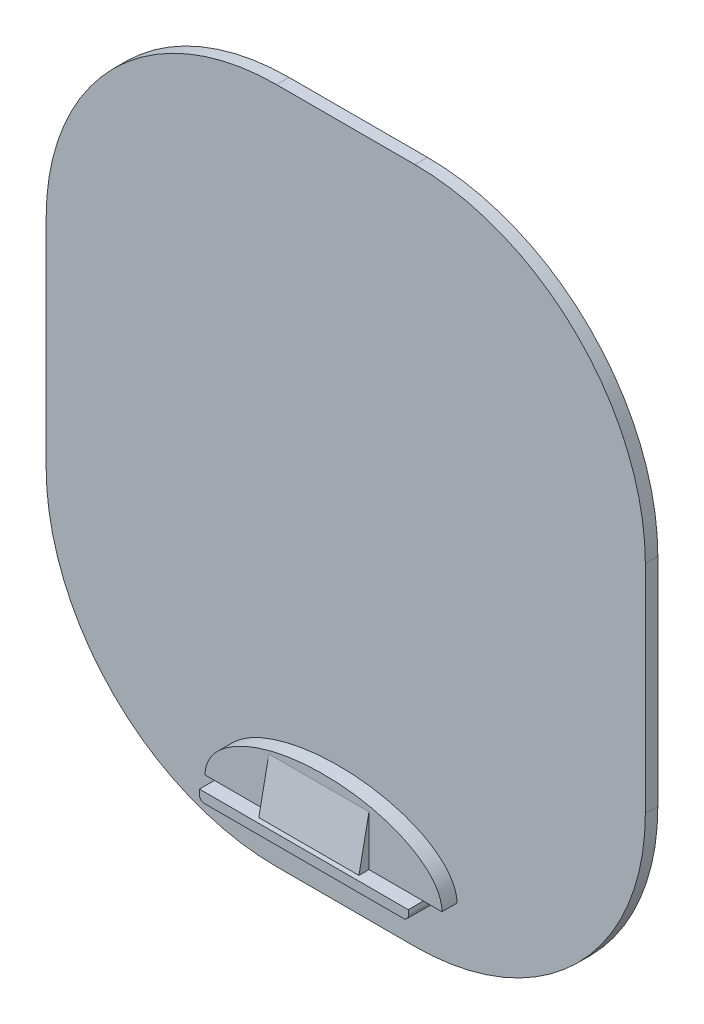
SolidWorks part; units mm, degrees
note: The reader was unsure of these and kept them because the rebuilt part matched: shared geometry of "Sketch15<3>".
ref_plane "Front Plane" through (0, 0, 0) normal (0, 0, 1) x (1, 0, 0)
ref_plane "Top Plane" through (0, 0, 0) normal (0, 1, 0) x (1, 0, 0)
ref_plane "Right Plane" through (0, 0, 0) normal (1, 0, 0) x (0, 0, -1)
sketch "Sketch1" plane through (0, 0, 0) normal (0, 0, 1) x (1, 0, 0)
  line L53 (241.5433, 205.3413) -> (246.9652, 204.9327)
  line L72 (-6.9957, 198.2293) -> (-6.9957, -78.6307)
  line L73 (35.8033, 153.9063) -> (35.8033, -34.3077)
  line L74 (69.2043, 274.4293) -> (259.7043, 274.4293)
  line L75 (335.9043, 198.2293) -> (335.9043, -78.6307)
  line L76 (259.7043, -154.8307) -> (69.2043, -154.8307)
  line L77 (87.2383, 205.3413) -> (241.5433, 205.3413)
  line L78 (35.8033, 153.9063) -> (35.8033, -34.3077)
  line L79 (87.2383, -85.7427) -> (238.612, -85.7427)
  line L80 (292.9783, 152.6781) -> (292.9783, -34.3077)
  line L81 (87.2383, -85.7427) -> (238.612, -85.7427)
  line L82 (292.9783, -34.3077) -> (292.9783, 152.6781)
  line L83 (241.5433, 205.3413) -> (87.2383, 205.3413)
  line L84 (-6.9957, 198.2293) -> (-6.9957, -78.6307)
  line L85 (69.2043, -154.8307) -> (259.7043, -154.8307)
  line L86 (335.9043, -78.6307) -> (335.9043, 198.2293)
  line L87 (259.7043, 274.4293) -> (69.2043, 274.4293)
  arc A32 (35.8033, -34.3077) -> (87.2383, -85.7427) centre (87.2383, -34.3077) ccw
  arc A33 (238.612, -85.7427) -> (292.9783, -34.3077) centre (238.612, -31.2928) ccw
  arc A34 (292.9783, 152.6781) -> (241.5433, 205.3413) centre (240.3004, 152.6781) ccw
  arc A35 (87.2383, 205.3413) -> (35.8033, 153.9063) centre (87.2383, 153.9063) ccw
  arc A36 (-6.9957, -78.6307) -> (69.2043, -154.8307) centre (69.2043, -78.6307) ccw
  arc A37 (259.7043, -154.8307) -> (335.9043, -78.6307) centre (259.7043, -78.6307) ccw
  arc A38 (335.9043, 198.2293) -> (259.7043, 274.4293) centre (259.7043, 198.2293) ccw
  arc A39 (69.2043, 274.4293) -> (-6.9957, 198.2293) centre (69.2043, 198.2293) ccw
  point P7 (-1548.8445, 807.057)
  point P171 (69.2043, 274.4293)
  point P172 (259.7043, 274.4293)
  point P173 (335.9043, 198.2293)
  point P174 (335.9043, -78.6307)
  point P175 (87.2383, 205.3413)
  point P176 (241.5433, 205.3413)
  point P181 (292.9783, 152.6781)
  point P182 (292.9783, -34.3077)
  point P183 (241.5433, -85.7427)
  point P184 (87.2383, -85.7427)
  point P185 (35.8033, -34.3077)
  point P186 (35.8033, 153.9063)
  point P187 (259.7043, -154.8307)
  point P188 (69.2043, -154.8307)
  point P200 (-6.9957, -78.6307)
  point P202 (-6.9957, 198.2293)
ref_plane "Plane1" through (0, 0, 10.16) normal (0, 0, 1) x (1, 0, 0)
ref_plane "Plane2" through (0, 0, 8.89) normal (0, 0, 1) x (1, 0, 0)
sketch "Sketch14" plane through (0, 0, 8.89) normal (0, 0, 1) x (1, 0, 0)
  line L20 (198.2363, 213.4693) -> (127.9259, 213.4693)
  line L21 (11.0859, -13.2857) -> (11.0859, 96.6293)
  line L22 (198.2363, -130.1257) -> (127.9259, -130.1257)
  line L23 (315.0763, 96.6293) -> (315.0763, -13.2857)
  arc A8 (315.0763, 96.6293) -> (198.2363, 213.4693) centre (198.2363, 96.6293) ccw
  arc A9 (127.9259, 213.4693) -> (11.0859, 96.6293) centre (127.9259, 96.6293) ccw
  arc A10 (127.9259, -130.1257) -> (11.0859, -13.2857) centre (127.9259, -13.2857) cw
  arc A11 (315.0763, -13.2857) -> (198.2363, -130.1257) centre (198.2363, -13.2857) cw
extrude "Boss-Extrude3" add sketch "Sketch14" along normal blind 6.35
sketch "Sketch15" plane through (0, 0, 15.24) normal (0, 0, 1) x (1, 0, 0)
  line L0 (99.3113, -100.3592) -> (219.5215, -100.3592)
  line L2 (99.3113, -100.3592) -> (219.5215, -100.3592)
  line L4 (106.6408, -105.4392) -> (207.5293, -105.4392)
  line L6 (104.1008, -100.3592) -> (210.0693, -100.3592)
  line L7 (104.1008, -100.3592) -> (104.1008, -102.8992)
  line L8 (104.1008, -105.4392) -> (210.0693, -105.4392)
  line L9 (210.0693, -100.3592) -> (210.0693, -102.8992)
  arc A0 (207.5293, -105.4392) -> (210.0693, -102.8992) centre (207.5293, -102.8992) ccw
  arc A1 (106.6408, -105.4392) -> (104.1008, -102.8992) centre (106.6408, -102.8992) cw
  ellipse E0 centre (159.4164, -100.3592) end of major axis (99.3113, -100.3592) minor radius 30.3646 (219.5215, -100.3592) -> (99.3113, -100.3592) ccw
  dimension "D2" = 2.54
  dimension "D1" = 5.08
extrude "Boss-Extrude4" add sketch "Sketch15" along normal blind 7.62 contours E0 L0
extrude "Boss-Extrude5" add sketch "Sketch15<3>" along normal blind 15.24
sketch "Sketch15<3>" plane through (0, 0, 15.24) normal (0, 0, 1) x (1, 0, 0) same geometry as "Sketch15"
ref_plane "Plane4" through (152.4, 0, 0) normal (1, 0, 0) x (0, 0, -1)
other "Gusset1" parameters "D1"=50.8, "D2"=50.8, "D3"=0, "D4"=0, "D10"=6.35, "D11"=25.4, "D12"=5.08, "D13"=12.7, "D14"=45, "D15"=12.7
sketch "Sketch19" plane through (157.085, -100.3592, 22.86) normal (1, 0, 0) x (0, 0, -1)
  line L0 (0, 0) -> (0, 25.4)
  line L1 (0, 0) -> (-5.08, 0)
  line L2 (0, 25.4) -> (-5.08, 0)
